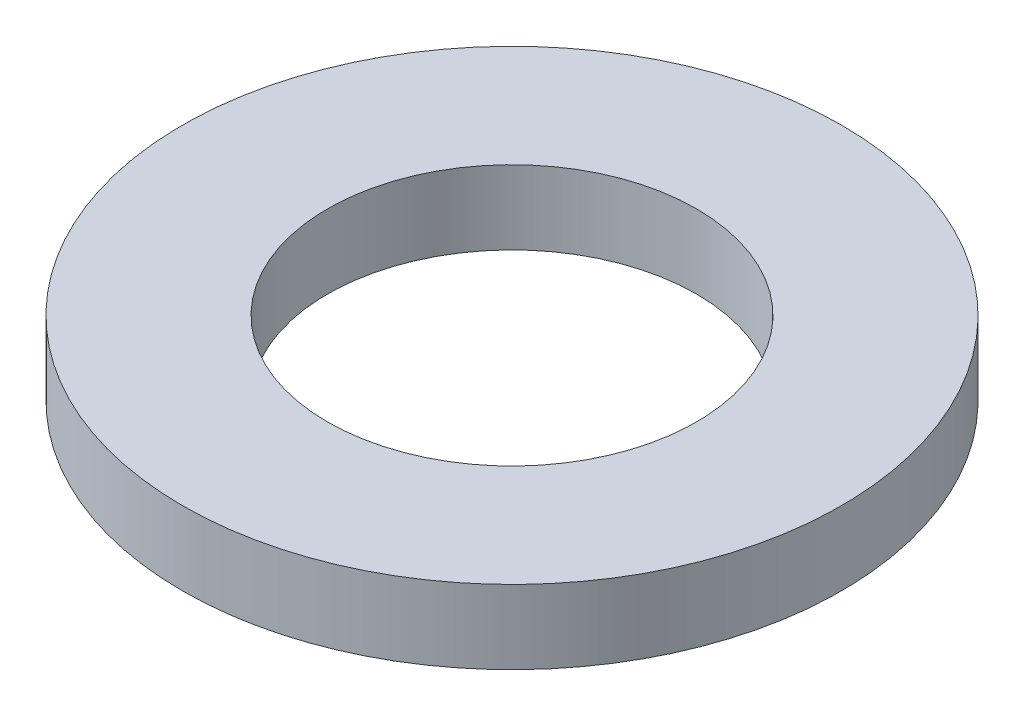
SolidWorks part; units mm, degrees
ref_plane "Front Plane" through (0, 0, 0) normal (0, 0, 1) x (1, 0, 0)
ref_plane "Top Plane" through (0, 0, 0) normal (0, 1, 0) x (1, 0, 0)
ref_plane "Right Plane" through (0, 0, 0) normal (1, 0, 0) x (0, 0, -1)
sketch "Sketch1" plane through (0, 0, 0) normal (0, 1, 0) x (1, 0, 0)
  circle A0 centre (0, 0) radius 62.5
  dimension "FLANGE_OD" = 125
extrude "Boss-Extrude1" add sketch "Sketch1" along normal blind 14
sketch "Sketch2" plane through (0, 0, 0) normal (0, 1, 0) x (1, 0, 0)
  circle A0 centre (0, 0) radius 35
  dimension "BORE_D" = 70
extrude "Cut-Extrude1" cut sketch "Sketch2" along normal through all
sketch "Sketch3" plane through (0, 14, 0) normal (0, 1, 0) x (1, 0, 0)
  circle A0 centre (0, 0) radius 27.046 construction
  circle A1 centre (-27.046, 0) radius 1.9317
  dimension "BOLT_D" = 3.8635
  dimension "BOLT_PCD" = 54.0921
extrude "Cut-Extrude2" cut sketch "Sketch3" against normal blind 10.9633 rebuild error yes
pattern_circular "CirPattern1" count 6 over 360 rebuild error yes
